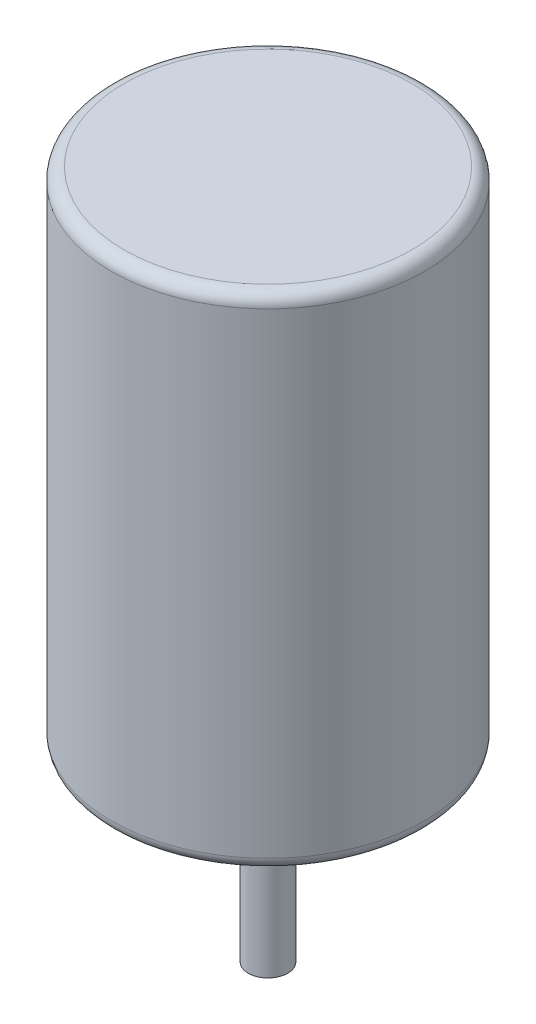
SolidWorks part; units mm, degrees
ref_plane "Front Plane" through (0, 0, 0) normal (0, 0, 1) x (1, 0, 0)
ref_plane "Top Plane" through (0, 0, 0) normal (0, 1, 0) x (1, 0, 0)
ref_plane "Right Plane" through (0, 0, 0) normal (1, 0, 0) x (0, 0, -1)
sketch "Sketch1" plane through (0, 0, 0) normal (0, 1, 0) x (1, 0, 0)
  circle A0 centre (0, 0) radius 25
  circle A1 centre (0, 0) radius 3.15
  dimension "D1" = 6.3
  dimension "D2" = 50
extrude "Boss-Extrude1" add sketch "Sketch1" along normal blind 80 contours A1 | A0 A1 region at (-24.2929, 0, 0) region at (0, 0, 0)
extrude "Boss-Extrude2" add sketch "Sketch1<2>" against normal blind 30 separate body contours A1 region at (0, 0, 0)
sketch "Sketch1<2>" plane through (0, 0, 0) normal (0, 1, 0) x (1, 0, 0) same geometry as "Sketch1"
fillet "Fillet1" radius 2 2 edges at (0, 0, 25) (0, 80, 25)
